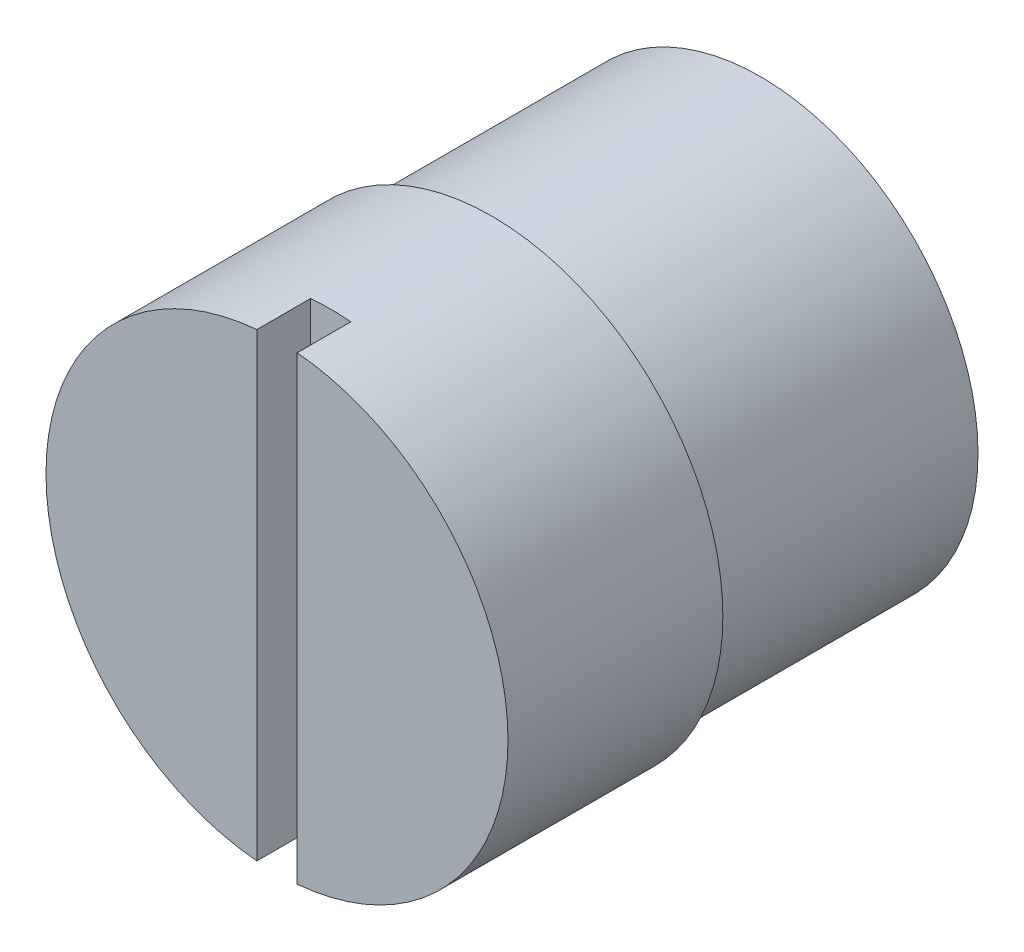
SolidWorks part; units mm, degrees
ref_plane "Front Plane" through (0, 0, 0) normal (0, 0, 1) x (1, 0, 0)
ref_plane "Top Plane" through (0, 0, 0) normal (0, 1, 0) x (1, 0, 0)
ref_plane "Right Plane" through (0, 0, 0) normal (1, 0, 0) x (0, 0, -1)
sketch "Sketch1" plane through (0, 0, 0) normal (0, 0, 1) x (1, 0, 0)
  circle A0 centre (0, 0) radius 2.55 construction
  circle A3 centre (0, 0) radius 2.35 construction
  circle A4 centre (0, 0) radius 4.05
  dimension "D1" = 4.7
  dimension "D2" = 0.2
  dimension "D3" = 1.5
extrude "Boss-Extrude1" add sketch "Sketch1" against normal blind 5
sketch "Sketch2" plane through (0, 0, 0) normal (0, 0, 1) x (1, 0, 0)
  circle A2 centre (0, 0) radius 4.3
  circle A3 centre (0, 0) radius 4.3
  dimension "D1" = 0.25
extrude "Boss-Extrude2" add sketch "Sketch2" along normal blind 4
sketch "Sketch4" plane through (0, 0, -5) normal (0, 0, -1) x (-1, 0, 0)
  point P0 (0, 0)
hole_wizard "M5x0.8 Tapped Hole1" positions "Sketch4" profile "Sketch6" tap size "M5x0.8" standard "ANSI Metric"
sketch "Sketch6" plane through (0, 0, -5) normal (1, 0, 0) x (0, 1, 0)
  line L0 (0, 0) -> (0, 5.6297)
  line L1 (0, 5.6297) -> (2.35, 5)
  line L2 (2.35, 5) -> (2.35, 0)
  line L5 (2.35, 0) -> (0, 0)
  line L10 (0, 5.6297) -> (-2.35, 5) construction
  line L11 (0, -6.35) -> (0, 107.95) construction
  dimension "Tap Drill Dia." = 4.7
  dimension "Tap Drill Depth" = 5
  dimension "Drill Angle" = 150
chamfer "Chamfer1" distance 0.5 angle 45 1 edges at (-2.35, 0, -5)
thread "Thread1" pitch 0.8 method cut profile "Thread Profile1" start angle 0, offset 1, length 5.5, pitch 0.8, diameter 4.7
ref_plane "Plane1" through (2.35, 0, -6) normal (0, -1, 0) x (1, 0, 0)
sketch "Thread Profile1" plane through (2.35, 0, -6) normal (0, -1, 0) x (1, 0, 0)
  line L0 (0, 0) -> (0, 0.8) construction
  line L1 (0, 0) -> (0.433, 0.25)
  line L2 (0.433, 0.25) -> (0.433, 0.35)
  line L3 (0.433, 0.35) -> (0, 0.6)
  line L4 (0.433, 0.3) -> (0, 0.3) construction
  line L11 (0, 0) -> (0, 0.6)
  point P2 (0, 0)
  dimension "Pitch" = 0.8
  dimension "Profile_Angle" = 60
  dimension "Profile_Land" = 0.1
  dimension "Profile_Height" = 0.433
sketch "Sketch3" plane through (0, 0, 4) normal (0, 0, 1) x (1, 0, 0)
  line L0 (0, 4.3) -> (0, -4.3) construction
  line L1 (-0.375, -4.3) -> (0.375, -4.3)
  line L2 (-0.375, 4.3) -> (0.375, 4.3)
  line L3 (0.375, -4.3) -> (0.375, 4.3)
  line L4 (-0.375, 4.3) -> (-0.375, -4.3)
  circle A0 centre (0, 0) radius 4.3 construction
  point P7 (0, 0)
  point P11 (0, -4.3)
  point P14 (0, 4.3)
  dimension "D1" = 0.75
extrude "Cut-Extrude1" cut sketch "Sketch3" against normal blind 1
equation "\"ThreadWalls\" = 1.5"
equation "\"D3@Sketch1\"=\"ThreadWalls\""
equation "\"BaseFlange\" = 0.25"
equation "\"D1@Sketch2\"=\"BaseFlange\""
